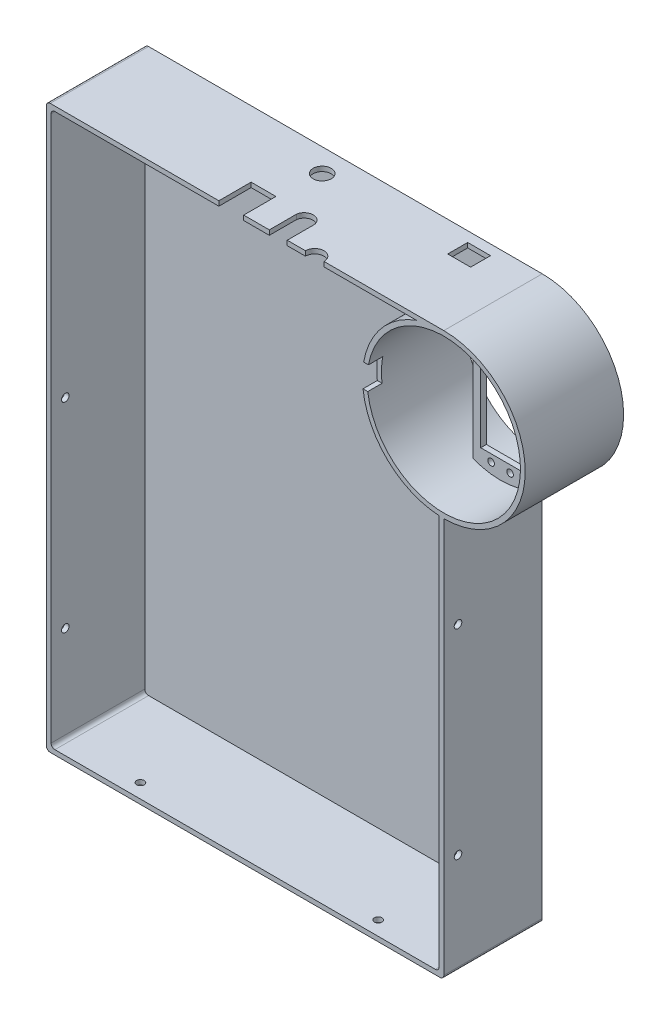
SolidWorks part; units mm, degrees
ref_plane "前视基准面" through (0, 0, 0) normal (0, 0, 1) x (1, 0, 0)
ref_plane "上视基准面" through (0, 0, 0) normal (0, 1, 0) x (1, 0, 0)
ref_plane "右视基准面" through (0, 0, 0) normal (1, 0, 0) x (0, 0, -1)
sketch "草图1" plane through (0, 0, 0) normal (0, 0, 1) x (1, 0, 0)
  line L0 (3.3953, 20.5) -> (10.5, 20.5)
  line L1 (-10.5, 20.5) -> (-3.3953, 20.5)
  line L2 (-10.5, 20.5) -> (-10.5, -20.5)
  line L3 (-10.5, -20.5) -> (10.5, -20.5)
  line L4 (10.5, 20.5) -> (10.5, -20.5)
  line L5 (-10.5, 20.5) -> (10.5, -20.5) construction
  line L6 (-10.5, -20.5) -> (10.5, 20.5) construction
  line L9 (-14.5, 48.1653) -> (-14.5, -27.4653)
  line L11 (14.5, 48.1653) -> (14.5, -27.4653)
  line L12 (-5.5897, 25.9626) -> (10.5, -18.9776) construction
  line L13 (-13.6514, -27.7799) -> (5.5897, 25.9626) construction
  circle A0 centre (-5, 24.315) radius 1.75
  circle A1 centre (5, 24.315) radius 1.75
  circle A2 centre (-5, -24.315) radius 1.75
  circle A3 centre (5, -24.315) radius 1.75
  arc A4 (-14.5, 48.1653) -> (-14.5, -27.4653) centre (0, 10.35) ccw
  circle A5 centre (0, 10.35) radius 43
  arc A6 (14.5, -27.4653) -> (14.5, 48.1653) centre (0, 10.35) ccw
  arc A7 (3.3953, 20.5) -> (-3.3953, 20.5) centre (0, 20.5) ccw
  point P0 (0, 0)
  dimension "D1" = 86
  dimension "D2" = 40.5
extrude "凸台-拉伸1" add sketch "草图1" along normal blind 3
sketch "草图3" plane through (0, 0, 0) normal (0, 0, -1) x (-1, 0, 0)
  circle A0 centre (0, 10.35) radius 43
extrude "拉伸-薄壁1" add sketch "草图3" along normal blind 19 and the other way blind 33 thin thin type one direction reverse wall 2.5
sketch "草图4" plane through (0, 0, -19) normal (0, 0, -1) x (-1, 0, 0)
  line L0 (0, -30.15) -> (32.498, -30.15) construction
  line L1 (0, 53.35) -> (210, 53.35)
  line L2 (0, -30.15) -> (0, -243.65)
  line L3 (0, -243.65) -> (210, -243.65)
  line L4 (210, 53.35) -> (210, -243.65)
  circle A0 centre (0, 10.35) radius 43 construction
  circle A1 centre (0, 10.35) radius 40.5 construction
  dimension "D1" = 210
  dimension "D2" = 297
extrude "拉伸-薄壁2" add sketch "草图4" against normal up to surface (52 mm away) thin up to face at (-40.5, 10.35, 33) thin type one direction reverse wall 2.5
sketch "草图5" plane through (0, 0, -19) normal (0, 0, -1) x (-1, 0, 0)
  line L4 (210, 53.35) -> (0, 53.35)
  line L5 (0, -32.65) -> (0, -243.65)
  line L6 (0, -243.65) -> (210, -243.65)
  line L7 (210, -243.65) -> (210, 53.35)
  line L8 (210, 53.35) -> (0, 53.35)
  line L9 (0, -32.65) -> (0, -243.65)
  line L10 (0, -243.65) -> (210, -243.65)
  line L11 (210, -243.65) -> (210, 53.35)
  arc A0 (0, -32.65) -> (0, 53.35) centre (0, 10.35) ccw
  arc A1 (0, 53.35) -> (0, -32.65) centre (0, 10.35) ccw
  line M12 (2.5, -241.15) -> (2.5, -32.5773)
  arc M13 (2.5, -32.5773) -> (14.4482, 50.85) centre (0, 10.35) ccw
  line M14 (14.4482, 50.85) -> (207.5, 50.85)
  line M15 (207.5, 50.85) -> (207.5, -241.15)
  line M16 (207.5, -241.15) -> (2.5, -241.15)
  dimension "D1" = 0
extrude "凸台-拉伸2" add sketch "草图5" against normal blind 2.5 contours M12 M16 M15 M14 M13 region at (-108.985, -100.0652, -19)
fillet "圆角1" radius 2 6 edges at (-207.5, 50.85, 8.25) (-207.5, -241.15, 8.25) (-2.5, -241.15, 8.25) (-210, 53.35, 7) (-210, -243.65, 7) (0, -243.65, 7)
sketch "草图6" plane through (0, 53.35, 0) normal (0, 1, 0) x (1, 0, 0)
  line L1 (-34.0289, 13.642) -> (-21.9602, 13.642)
  line L2 (-34.0289, 13.642) -> (-34.0289, 3.1093)
  line L3 (-34.0289, 3.1093) -> (-21.9602, 3.1093)
  line L4 (-21.9602, 13.642) -> (-21.9602, 3.1093)
extrude "切除-拉伸1" cut sketch "草图6" against normal blind 3
sketch "草图7" plane through (0, 0, 0) normal (1, 0, 0) x (0, 0, -1)
  circle A0 centre (-25.5, -84.8011) radius 2
  circle A1 centre (-25.5, -190.3505) radius 2
extrude "切除-拉伸2" cut sketch "草图7" against normal blind 283
sketch "草图8" plane through (0, -243.65, 0) normal (0, -1, 0) x (1, 0, 0)
  circle A0 centre (-167.8079, 25.5) radius 2
  circle A1 centre (-42.1921, 25.5) radius 2
extrude "切除-拉伸3" cut sketch "草图8" against normal blind 10
sketch "草图9" plane through (0, 53.35, 0) normal (0, 1, 0) x (1, 0, 0)
  line L1 (-118.8557, -15.9726) -> (-105.7388, -15.9726)
  line L2 (-118.8557, -15.9726) -> (-118.8557, -35.692)
  line L3 (-118.8557, -35.692) -> (-105.7388, -35.692)
  line L4 (-105.7388, -15.9726) -> (-105.7388, -35.692)
  line L5 (-92.2101, -34.2237) -> (-82.7401, -34.2237)
  line L6 (-92.2101, -34.2237) -> (-92.2101, -18.6195)
  line L8 (-82.7401, -34.2237) -> (-82.7401, -18.6195)
  arc A0 (-92.2101, -18.6195) -> (-82.7401, -18.6195) centre (-87.4751, -19.2834) cw
extrude "切除-拉伸4" cut sketch "草图9" against normal blind 10
sketch "草图10" plane through (-2.5, 0, 0) normal (-1, 0, 0) x (0, 0, 1)
  line L0 (33, 51.35) -> (33, -241.65) construction
  line L1 (33, 17.7663) -> (25.4404, 17.7663)
  line L2 (33, 17.7663) -> (33, 5.3712)
  line L3 (33, 5.3712) -> (25.4404, 5.3712)
  line L4 (25.4404, 17.7663) -> (25.4404, 5.3712)
extrude "切除-拉伸5" cut sketch "草图10" along normal blind 61
sketch "草图11" plane through (0, 0, -19) normal (0, 0, -1) x (-1, 0, 0)
  line L1 (87.2747, 34.8257) -> (99.1548, 34.8257)
  line L2 (87.2747, 34.8257) -> (87.2747, 12.9664)
  line L3 (87.2747, 12.9664) -> (99.1548, 12.9664)
  line L4 (99.1548, 34.8257) -> (99.1548, 12.9664)
extrude "切除-拉伸6" cut sketch "草图11" against normal blind 61
sketch "草图12" plane through (0, 53.35, 0) normal (0, 1, 0) x (1, 0, 0)
  line L0 (-104, 19) -> (-104, -33) construction
  line L1 (-208, 19) -> (0, 19) construction
  line L2 (-92.2101, -33) -> (-105.7388, -33) construction
  circle A0 centre (-104, 6.7385) radius 4.8
extrude "切除-拉伸7" cut sketch "草图12" against normal blind 10
sketch "草图13" plane through (0, 53.35, 0) normal (0, 1, 0) x (1, 0, 0)
  line L0 (0, -33) -> (-82.7401, -33) construction
  circle A0 centre (-68.2217, -33) radius 4.9066
extrude "切除-拉伸8" cut sketch "草图13" against normal blind 10
sketch "草图14" plane through (0, 0, -19) normal (0, 0, -1) x (-1, 0, 0)
  line L1 (243.7926, -109.8192) -> (-67.999, -109.8192)
  line L2 (243.7926, -109.8192) -> (243.7926, 61.4883)
  line L3 (243.7926, 61.4883) -> (-67.999, 61.4883)
  line L4 (-67.999, -109.8192) -> (-67.999, 61.4883)
extrude "切除-拉伸9" [suppressed] cut sketch "草图14" against normal blind 80 flip side to cut
